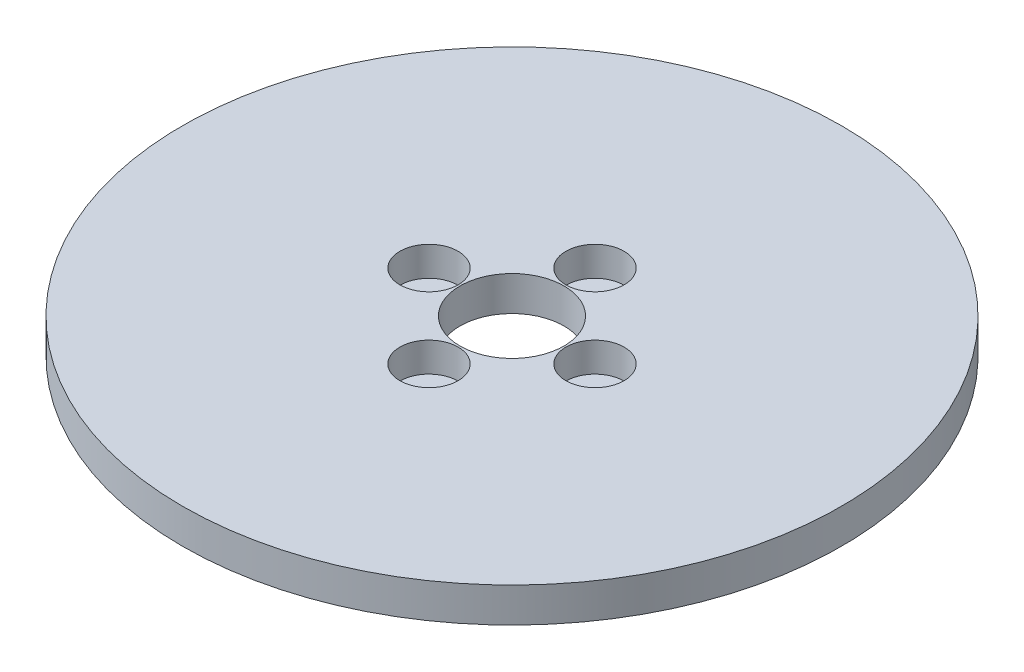
SolidWorks part; units mm, degrees
ref_plane "Front Plane" through (0, 0, 0) normal (0, 0, 1) x (1, 0, 0)
ref_plane "Top Plane" through (0, 0, 0) normal (0, 1, 0) x (1, 0, 0)
ref_plane "Right Plane" through (0, 0, 0) normal (1, 0, 0) x (0, 0, -1)
sketch "Sketch1" plane through (0, 0, 0) normal (0, 1, 0) x (1, 0, 0)
  circle A0 centre (0, 0) radius 47.5
  dimension "FLANGE_OD" = 95
extrude "Boss-Extrude1" add sketch "Sketch1" along normal blind 5
sketch "Sketch2" plane through (0, 0, 0) normal (0, 1, 0) x (1, 0, 0)
  circle A0 centre (0, 0) radius 7.5
  dimension "BORE_D" = 15
extrude "Cut-Extrude1" cut sketch "Sketch2" along normal through all
sketch "Sketch3" plane through (0, 5, 0) normal (0, 1, 0) x (1, 0, 0)
  circle A0 centre (0, 0) radius 11.9621 construction
  circle A1 centre (-11.9621, 0) radius 4.1994
  dimension "BOLT_D" = 8.3989
  dimension "BOLT_PCD" = 23.9242
extrude "Cut-Extrude2" cut sketch "Sketch3" against normal blind 4.2459
pattern_circular "CirPattern1" count 4 over 360 about axis through (0, 0, 0) along (0, 1, 0) of "Cut-Extrude2"
